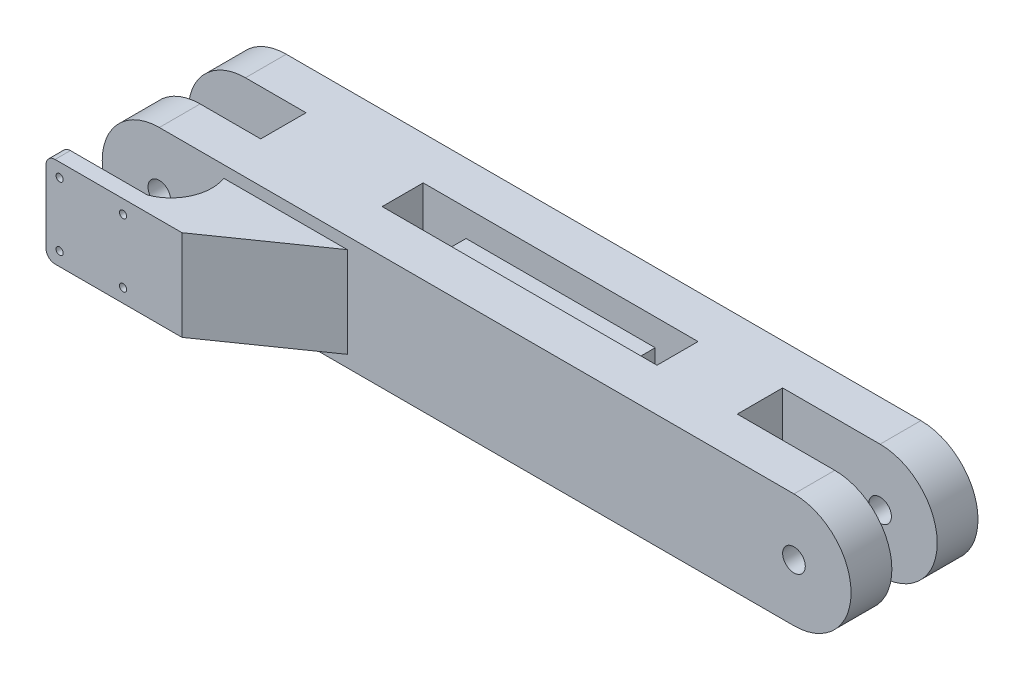
SolidWorks part; units mm, degrees
ref_plane "Front" through (0, 0, 0) normal (0, 0, 1) x (1, 0, 0)
ref_plane "Top" through (0, 0, 0) normal (0, 1, 0) x (1, 0, 0)
ref_plane "Right" through (0, 0, 0) normal (1, 0, 0) x (0, 0, -1)
sketch "Sketch1" plane through (0, 0, 0) normal (0, 0, 1) x (1, 0, 0)
  line L0 (-47.2174, -8.0761) -> (130.5826, -8.0761) construction
  line L1 (-47.2174, 7.9239) -> (130.5826, 7.9239)
  line L2 (-47.2174, -24.0761) -> (130.5826, -24.0761)
  arc A0 (-47.2174, 7.9239) -> (-47.2174, -24.0761) centre (-47.2174, -8.0761) ccw
  arc A1 (130.5826, -24.0761) -> (130.5826, 7.9239) centre (130.5826, -8.0761) ccw
  circle A2 centre (-47.2174, -8.0761) radius 3.175
  circle A3 centre (130.5826, -8.0761) radius 3.175
  point P2 (41.6826, -8.0761)
  dimension "D1" = 16
  dimension "D3" = 6.35
  dimension "D4" = 6.35
  dimension "D2" = 177.8
extrude "Boss-Extrude1" add sketch "Sketch1" along normal blind 11.43
sketch "Sketch2" plane through (0, 0, 11.43) normal (0, 0, 1) x (1, 0, 0)
  line L2 (-39.1367, -24.0761) -> (-39.1367, 7.9239)
  line L4 (130.5826, 7.9239) -> (-47.2174, 7.9239) construction
  line L7 (-47.2174, -24.0761) -> (130.5826, -24.0761) construction
  line L9 (122.3276, -24.0761) -> (122.3276, 7.9239)
  line L10 (-39.1367, 7.9239) -> (122.3276, 7.9239)
  line L11 (-39.1367, -24.0761) -> (122.3276, -24.0761)
  point P13 (-39.1367, -8.0761)
  point P16 (16.9972, 0.4239)
  point P24 (122.3276, -8.0761)
extrude "Boss-Extrude2" add sketch "Sketch2" along normal blind 12.7
sketch "Sketch5" plane through (0, 0, 24.13) normal (0, 0, 1) x (1, 0, 0)
  line L0 (-47.2174, -8.0761) -> (130.5826, -8.0761) construction
  line L1 (-47.2174, 7.9239) -> (130.5826, 7.9239)
  line L2 (-47.2174, -24.0761) -> (130.5826, -24.0761)
  arc A0 (-47.2174, 7.9239) -> (-47.2174, -24.0761) centre (-47.2174, -8.0761) ccw
  arc A1 (130.5826, -24.0761) -> (130.5826, 7.9239) centre (130.5826, -8.0761) ccw
  circle A2 centre (-47.2174, -8.0761) radius 3.175
  circle A3 centre (130.5826, -8.0761) radius 3.175
  point P4 (41.6826, -8.0761)
  dimension "D1" = 16
  dimension "D2" = 6.35
  dimension "D3" = 6.35
extrude "Boss-Extrude3" add sketch "Sketch5" along normal blind 11.43
sketch "Sketch6" plane through (0, 7.9239, 0) normal (0, 1, 0) x (1, 0, 0)
  line L0 (41.6826, 0) -> (41.6826, -35.56)
  line L1 (130.5826, 0) -> (-47.2174, 0) construction
  line L2 (130.5826, -35.56) -> (-47.2174, -35.56) construction
  line L3 (-39.1367, -17.78) -> (122.3276, -17.78)
  line L4 (-39.1367, -24.13) -> (-39.1367, -11.43) construction
  line L5 (122.3276, -24.13) -> (122.3276, -11.43) construction
  line L7 (3.1826, -23.53) -> (80.1826, -23.53)
  line L8 (3.1826, -23.53) -> (3.1826, -12.03)
  line L9 (3.1826, -12.03) -> (80.1826, -12.03)
  line L10 (80.1826, -23.53) -> (80.1826, -12.03)
  line L11 (3.1826, -23.53) -> (80.1826, -12.03) construction
  line L12 (3.1826, -12.03) -> (80.1826, -23.53) construction
  point P12 (41.6826, -17.78)
extrude "Cut-Extrude1" cut sketch "Sketch6" against normal blind 7.5 contours L7 L10 L9 L8
sketch "Sketch7" plane through (0, 0.4239, 0) normal (0, 1, 0) x (1, 0, 0)
  line L5 (3.1826, -23.53) -> (80.1826, -23.53) construction
  line L10 (3.1826, -12.03) -> (15.1826, -12.03)
  line L11 (3.1826, -12.03) -> (3.1826, -23.53)
  line L12 (3.1826, -23.53) -> (15.1826, -23.53)
  line L13 (15.1826, -12.03) -> (15.1826, -23.53)
  line L14 (3.1826, -12.03) -> (80.1826, -12.03) construction
  line L15 (80.1826, -23.53) -> (68.1826, -23.53)
  line L16 (80.1826, -23.53) -> (80.1826, -12.03)
  line L17 (80.1826, -12.03) -> (68.1826, -12.03)
  line L18 (68.1826, -23.53) -> (68.1826, -12.03)
sketch "Sketch10" plane through (0, 0, 35.56) normal (0, 0, 1) x (1, 0, 0)
  line L0 (-47.2174, -24.0761) -> (130.5826, -24.0761) construction
  line L1 (-34.5174, -20.7761) -> (-57.3774, -20.7761)
  line L3 (-34.5174, 4.6239) -> (-57.3774, 4.6239)
  line L4 (-59.9174, -18.2361) -> (-59.9174, 2.0839)
  line L5 (-34.5174, -20.7761) -> (-59.9174, 4.6239) construction
  line L6 (-34.5174, 4.6239) -> (-59.9174, -20.7761) construction
  line L7 (-34.5174, 4.6239) -> (-21.8174, 4.6239)
  line L9 (-34.5174, -20.7761) -> (-21.8174, -20.7761)
  line L10 (-21.8174, 4.6239) -> (-21.8174, -20.7761)
  arc A1 (-57.3774, -20.7761) -> (-59.9174, -18.2361) centre (-57.3774, -18.2361) cw
  arc A2 (-57.3774, 4.6239) -> (-59.9174, 2.0839) centre (-57.3774, 2.0839) ccw
  dimension "D1" = 2.54
  dimension "D2" = 35.56
  dimension "D3" = 25.4
  dimension "D4" = 12.7
  dimension "D5" = 3.3
extrude "Boss-Extrude4" add sketch "Sketch10" along normal blind 19.05 contours L4 A2 L3 L7 L10 L9 L1 A1
sketch "Sketch14" plane through (0, 4.6239, 0) normal (0, 1, 0) x (1, 0, 0)
  line L0 (-59.9174, -35.56) -> (-29.1834, -35.56)
  line L1 (-56.9493, -35.56) -> (-21.8174, -35.56) construction
  line L2 (-59.9174, -35.56) -> (-59.9174, -50.3102)
  line L3 (-59.9174, -54.61) -> (-59.9174, -35.56) construction
  line L4 (-59.9174, -50.3102) -> (-35.7956, -50.3102)
  arc A0 (-29.1834, -35.56) -> (-35.7956, -50.3102) centre (-39.8646, -39.629) cw
  dimension "D1" = 11.43
  dimension "D2" = 24.1218
  dimension "D3" = 14.7502
  dimension "D4" = 30.734
extrude "Cut-Extrude3" cut sketch "Sketch14" against normal blind 30.48
sketch "Sketch15" plane through (0, -20.7761, 0) normal (0, -1, 0) x (1, 0, 0)
  line L0 (-21.8174, 35.56) -> (5.4637, 35.56)
  line L1 (-47.2174, 35.56) -> (130.5826, 35.56) construction
  line L2 (-21.8174, 54.61) -> (5.4637, 35.56)
  line L3 (-21.8174, 54.61) -> (-21.8174, 35.56)
extrude "Boss-Extrude5" add sketch "Sketch15" against normal blind 25.4
extrude "Cut-Extrude4" cut sketch "Sketch7" against normal blind 50.8 contours L18 L17 L16 L15
extrude "Cut-Extrude5" cut sketch "Sketch7<5>" against normal blind 50.8 contours L13 L12 L11 L10
sketch "Sketch7<5>" plane through (0, 0.4239, 0) normal (0, 1, 0) x (1, 0, 0) same geometry as "Sketch7"
sketch "Sketch16" plane through (-39.1367, 0, 0) normal (-1, 0, 0) x (0, 0, 1)
  line L1 (11.43, 7.9239) -> (24.13, 7.9239)
  line L2 (11.43, 7.9239) -> (11.43, -24.0761)
  line L3 (11.43, -24.0761) -> (24.13, -24.0761)
  line L4 (24.13, 7.9239) -> (24.13, -24.0761)
extrude "Cut-Extrude6" cut sketch "Sketch16" against normal blind 8.89
sketch "Sketch17" plane through (0, 0, 50.3102) normal (0, 0, -1) x (-1, 0, 0)
  line L0 (47.2174, 4.6239) -> (47.2174, -20.7761) construction
  line L1 (57.3774, 4.6239) -> (35.7956, 4.6239) construction
  line L2 (35.7956, -20.7761) -> (57.3774, -20.7761) construction
  line L3 (35.7868, -8.0761) -> (59.9174, -8.0761) construction
  line L4 (59.9174, -18.2361) -> (59.9174, 2.0839) construction
  circle A0 centre (47.2174, -8.0761) radius 3.175 construction
  circle A1 centre (47.2174, -8.0761) radius 3.175
  circle A2 centre (56.1074, 0.8139) radius 1
  circle A3 centre (56.1074, -16.9661) radius 1
  circle A4 centre (38.3274, -16.9661) radius 1
  circle A5 centre (38.3274, 0.8139) radius 1
  dimension "D3" = 2
  dimension "D1" = 17.78
  dimension "D2" = 17.78
extrude "Cut-Extrude7" cut sketch "Sketch17" against normal up to surface (4.2998 mm away) contours A5 | A2 | A3 | A4 region at (-56.1074, 0.8139, 50.3102) region at (-56.1074, -16.9661, 50.3102) region at (-38.3274, 0.8139, 50.3102) up to face at (-46.5461, -8.0761, 54.61)
sketch "Sketch18" plane through (122.3276, 0, 0) normal (1, 0, 0) x (0, 0, -1)
  line L1 (-24.13, 7.9239) -> (-11.43, 7.9239)
  line L2 (-24.13, 7.9239) -> (-24.13, -24.0761)
  line L3 (-24.13, -24.0761) -> (-11.43, -24.0761)
  line L4 (-11.43, 7.9239) -> (-11.43, -24.0761)
extrude "Cut-Extrude8" cut sketch "Sketch18" against normal blind 19.05
